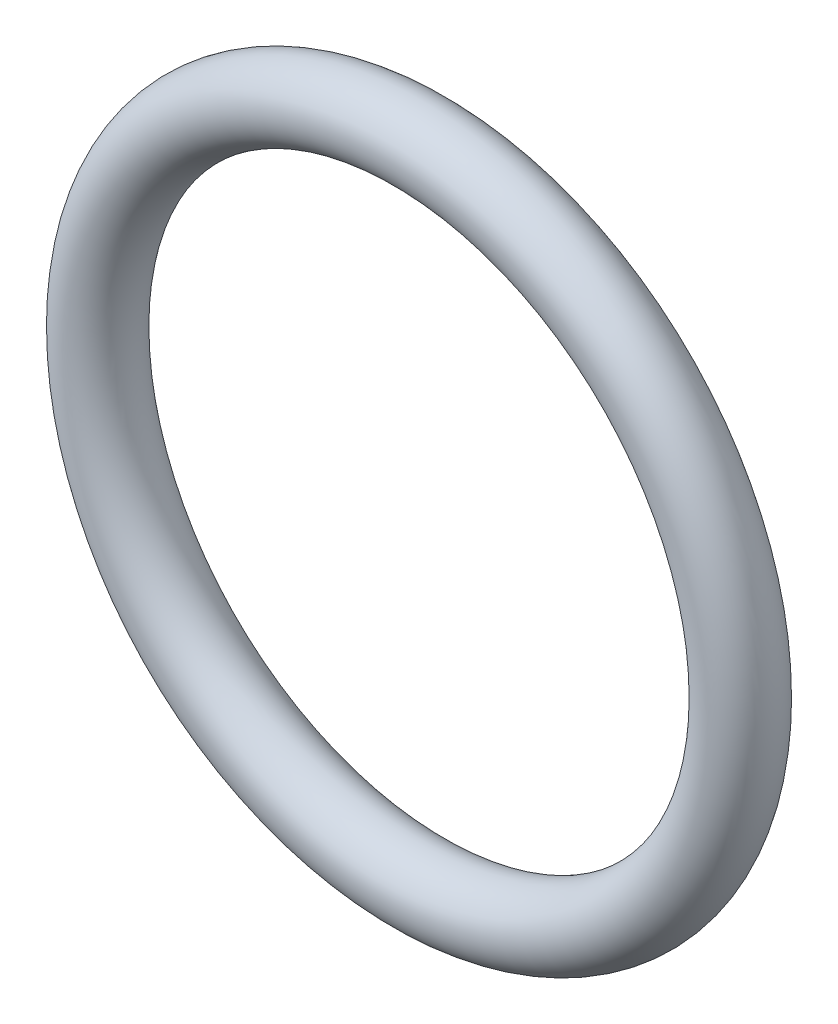
SolidWorks part; units mm, degrees
ref_plane "Front Plane" through (0, 0, 0) normal (0, 0, 1) x (1, 0, 0)
ref_plane "Top Plane" through (0, 0, 0) normal (0, 1, 0) x (1, 0, 0)
ref_plane "Right Plane" through (0, 0, 0) normal (1, 0, 0) x (0, 0, -1)
sketch "Sketch1" plane through (0, 0, 0) normal (1, 0, 0) x (0, 0, -1)
  line L0 (-7.452, 0) -> (8.2521, 0) construction
  line L1 (0, 6.9977) -> (0, 0) construction
  circle A0 centre (0, 7.8867) radius 0.889
  dimension "D1" = 1.778
  dimension "D2" = 13.9954
revolve "Revolve1" add sketch "Sketch1" angle 360 about L0
ref_axis "Axis1" [suppressed] through (0, 0, 0.9779) along (0, 0, -1)
